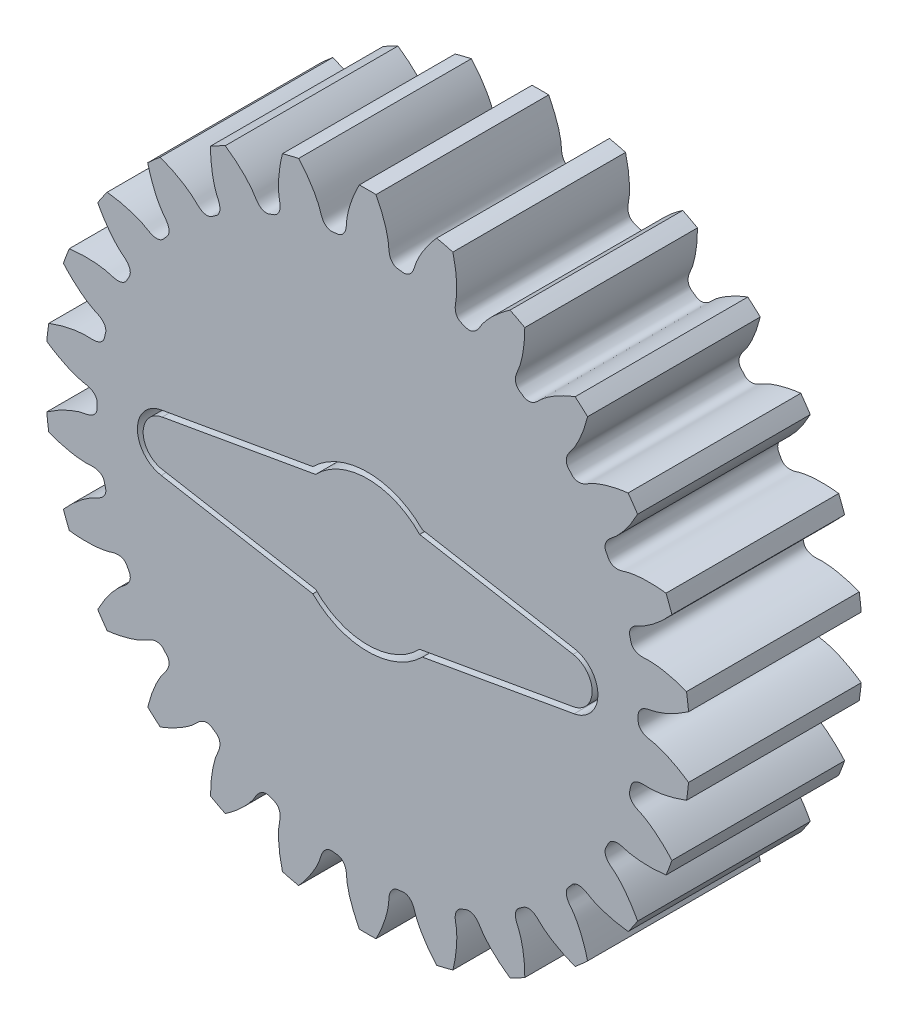
SolidWorks part; units mm, degrees
ref_plane "Front Plane" through (0, 0, 0) normal (0, 0, 1) x (1, 0, 0)
ref_plane "Top Plane" through (0, 0, 0) normal (0, 1, 0) x (1, 0, 0)
ref_plane "Right Plane" through (0, 0, 0) normal (1, 0, 0) x (0, 0, -1)
ref_axis "Axis1" through (0, 0, 55) along (0, 0, -1)
sketch "旋转草图小直齿轮" plane through (0, 0, 0) normal (1, 0, 0) x (0, 0, -1)
  line L0 (0, 0) -> (1, 0) construction
  line L1 (-7.5, 0) -> (-7.5, 28)
  line L2 (-7.5, 28) -> (7.5, 28)
  line L3 (7.5, 28) -> (7.5, 0)
  line L4 (7.5, 0) -> (-7.5, 0)
  dimension "Side1" = 7.5
  dimension "OutsideRadius" = 28
  dimension "Side2" = 7.5
revolve "小直齿轮" add sketch "旋转草图小直齿轮" angle 360 about L0
sketch "齿草图小直齿轮" plane through (0, 0, 0) normal (0, 0, 1) x (1, 0, 0)
  arc A0 (27.9679, 2.7212) -> (27.9679, -2.7212) centre (0, 0) cw
  spline S0 degree 3 poles (27.9679, -2.7212) (27.7638, -2.5774) (27.4599, -2.3753) (27.0547, -2.1308) (26.7715, -1.9706) (26.5013, -1.8278) (26.2448, -1.7014) (26.0028, -1.5905) (25.7759, -1.4943) (25.5647, -1.4117) (25.3698, -1.3417) (25.1918, -1.2835) (25.0311, -1.2359) (24.8881, -1.198) (24.7634, -1.1686) (24.6015, -1.1352) (24.461, -1.1147) (24.34, -1.0852) (24.2853, -1.0704) (24.2318, -1.0542) (24.1794, -1.0366) (24.1279, -1.0175) (24.0774, -0.9966) (24.0276, -0.9738) (23.9785, -0.9488) (23.9299, -0.9214) (23.8818, -0.891) (23.8341, -0.8573) (23.7869, -0.8195) (23.7403, -0.777) (23.6946, -0.7291) (23.6504, -0.6747) (23.6089, -0.6131) (23.5712, -0.5439) (23.5394, -0.4668) (23.5153, -0.3828) (23.502, -0.2987) (23.4964, -0.1705) (23.5027, 0) (23.4964, 0.1705) (23.502, 0.2987) (23.5153, 0.3828) (23.5394, 0.4668) (23.5712, 0.5439) (23.6089, 0.6131) (23.6504, 0.6747) (23.6946, 0.7291) (23.7403, 0.777) (23.7869, 0.8195) (23.8341, 0.8573) (23.8818, 0.891) (23.9299, 0.9214) (23.9785, 0.9488) (24.0276, 0.9738) (24.0774, 0.9966) (24.1279, 1.0175) (24.1794, 1.0366) (24.2318, 1.0542) (24.2853, 1.0704) (24.34, 1.0852) (24.461, 1.1147) (24.6015, 1.1352) (24.7634, 1.1686) (24.8881, 1.198) (25.0311, 1.2359) (25.1918, 1.2835) (25.3698, 1.3417) (25.5647, 1.4117) (25.7759, 1.4943) (26.0028, 1.5905) (26.2448, 1.7014) (26.5013, 1.8278) (26.7715, 1.9706) (27.0547, 2.1308) (27.4599, 2.3753) (27.7638, 2.5774) (27.9679, 2.7212) knots 0 0 0 0 0.067642 0.098793 0.128164 0.155755 0.181566 0.205597 0.227848 0.248319 0.267009 0.28392 0.29905 0.312401 0.323971 0.333762 0.357174 0.362366 0.367478 0.37252 0.377507 0.382456 0.387386 0.39232 0.397282 0.402306 0.407425 0.41268 0.418119 0.423791 0.429751 0.436051 0.442738 0.449842 0.457364 0.465268 0.473469 0.480354 0.5 0.519646 0.526531 0.534732 0.542636 0.550158 0.557262 0.563949 0.570249 0.576209 0.581881 0.58732 0.592575 0.597694 0.602718 0.60768 0.612614 0.617544 0.622493 0.62748 0.632522 0.637634 0.642826 0.666238 0.676029 0.687599 0.70095 0.71608 0.732991 0.751681 0.772152 0.794403 0.818434 0.844245 0.871836 0.901207 0.932358 1 1 1 1
extrude "齿拉伸切除小直齿轮" cut sketch "齿草图小直齿轮" against normal blind 7.5 and the other way blind 7.5
pattern_circular "齿形小直齿轮" count 26 every 13.846 about axis through (0, 0, 55) along (0, 0, -1) of "齿拉伸切除小直齿轮"
sketch "辅助草图小直齿轮" plane through (0, 0, 0) normal (0, 0, 1) x (1, 0, 0)
  circle A0 centre (0, 0) radius 26 construction
  circle A1 centre (0, 0) radius 24.432 construction
  circle A2 centre (0, 0) radius 24.5849 construction
  circle A3 centre (0, 0) radius 28 construction
  circle A4 centre (0, 0) radius 23.5 construction
  dimension "PitchDiameter" = 52
  dimension "BaseDiameter" = 48.864
  dimension "FormDiameter" = 49.1697
  dimension "MajorDiameter" = 56
  dimension "MinorDiameter" = 47
sketch "Sketch5" plane through (0, 0, 7.5) normal (0, 0, 1) x (1, 0, 0)
  circle A0 centre (0, 0) radius 1.5
  dimension "D1" = 3
extrude "Extrude2" cut sketch "Sketch5" against normal through all
sketch "Sketch6" plane through (0, 0, 7.5) normal (0, 0, 1) x (1, 0, 0)
  line L0 (20, 0) -> (-20, 0) construction
  line L1 (17.9341, -2.462) -> (4.7611, -4.7848)
  line L2 (17.9341, 2.462) -> (4.7611, 4.7848)
  line L3 (0, 0) -> (0, -13.8039) construction
  line L4 (-17.9341, 2.462) -> (-4.7611, 4.7848)
  line L5 (-17.9341, -2.462) -> (-4.7611, -4.7848)
  arc A0 (4.7611, 4.7848) -> (-4.7611, 4.7848) centre (0, 0) ccw
  arc A1 (-17.9341, -2.462) -> (-17.9341, 2.462) centre (-17.5, 0) cw
  arc A2 (17.9341, -2.462) -> (17.9341, 2.462) centre (17.5, 0) ccw
  arc A4 (-4.7611, -4.7848) -> (4.7611, -4.7848) centre (0, 0) ccw
  point P6 (0, 0)
  dimension "D1" = 13.5
  dimension "D4" = 5
  dimension "D2" = 40
  dimension "D6" = 20
extrude "Extrude3" cut sketch "Sketch6" against normal blind 2.5
sketch "Sketch7" plane through (0, 0, -7.5) normal (0, 0, -1) x (-1, 0, 0)
  line L0 (0, 0) -> (-8.197, 22.0229)
  spline S0 degree 3 poles (-12.3671, 25.1208) (-12.1929, 25.0009) (-11.9283, 24.8095) (-11.586, 24.541) (-11.3359, 24.333) (-11.1065, 24.131) (-10.8974, 23.936) (-10.7079, 23.7491) (-10.5374, 23.571) (-10.3853, 23.4028) (-10.2508, 23.2454) (-10.1332, 23.0996) (-10.0318, 22.9662) (-9.9456, 22.846) (-9.8739, 22.7398) (-9.7852, 22.6003) (-9.7162, 22.4762) (-9.6457, 22.3735) (-9.6125, 22.3276) (-9.5784, 22.2833) (-9.5434, 22.2405) (-9.5072, 22.1992) (-9.4698, 22.1593) (-9.4308, 22.1209) (-9.39, 22.0838) (-9.3472, 22.0481) (-9.3017, 22.0139) (-9.2533, 21.9813) (-9.2012, 21.9505) (-9.145, 21.922) (-9.0839, 21.8963) (-9.0174, 21.8743) (-8.9451, 21.8572) (-8.867, 21.8466) (-8.7837, 21.8441) (-8.6966, 21.8515) (-8.6132, 21.8689) (-8.4913, 21.909) (-8.3342, 21.9754) (-8.1725, 22.0299) (-8.0546, 22.0807) (-7.9807, 22.123) (-7.9107, 22.1752) (-7.8499, 22.2323) (-7.7985, 22.2921) (-7.7557, 22.3528) (-7.7205, 22.4133) (-7.6919, 22.4731) (-7.6687, 22.5317) (-7.6501, 22.5893) (-7.6355, 22.6458) (-7.6242, 22.7016) (-7.6157, 22.7567) (-7.6098, 22.8115) (-7.6061, 22.8661) (-7.6045, 22.9208) (-7.6049, 22.9757) (-7.607, 23.031) (-7.6109, 23.0867) (-7.6164, 23.1431) (-7.6318, 23.2667) (-7.6624, 23.4053) (-7.6885, 23.5686) (-7.7053, 23.6956) (-7.7205, 23.8427) (-7.733, 24.0099) (-7.7417, 24.197) (-7.7454, 24.404) (-7.7431, 24.6308) (-7.7336, 24.8771) (-7.7157, 25.1427) (-7.6885, 25.4273) (-7.6508, 25.7306) (-7.6014, 26.0522) (-7.5233, 26.4801) (-7.4521, 26.7988) (-7.4013, 27.0041) knots 0.010365 0.010365 0.010365 0.010365 0.067642 0.098793 0.128164 0.155755 0.181566 0.205597 0.227848 0.248319 0.267009 0.28392 0.29905 0.312401 0.323971 0.333762 0.357174 0.362366 0.367478 0.37252 0.377507 0.382456 0.387386 0.39232 0.397282 0.402306 0.407425 0.41268 0.418119 0.423791 0.429751 0.436051 0.442738 0.449842 0.457364 0.465268 0.473469 0.480354 0.5 0.519646 0.526531 0.534732 0.542636 0.550158 0.557262 0.563949 0.570249 0.576209 0.581881 0.58732 0.592575 0.597694 0.602718 0.60768 0.612614 0.617544 0.622493 0.62748 0.632522 0.637634 0.642826 0.666238 0.676029 0.687599 0.70095 0.71608 0.732991 0.751681 0.772152 0.794403 0.818434 0.844245 0.871836 0.901207 0.932358 0.989635 0.989635 0.989635 0.989635 construction
sketch "Sketch8" plane through (0, 0, 5) normal (0, 0, 1) x (1, 0, 0)
  line L8 (-17.8473, -1.9696) -> (-4.5165, -4.3202)
  line L9 (4.5165, -4.3202) -> (17.8473, -1.9696)
  line L10 (17.8473, 1.9696) -> (4.5165, 4.3202)
  line L11 (-4.5165, 4.3202) -> (-17.8473, 1.9696)
  line L12 (-17.8473, -1.9696) -> (-4.5165, -4.3202)
  line L13 (4.5165, -4.3202) -> (17.8473, -1.9696)
  line L14 (17.8473, 1.9696) -> (4.5165, 4.3202)
  line L15 (-4.5165, 4.3202) -> (-17.8473, 1.9696)
  arc A8 (-17.8473, 1.9696) -> (-17.8473, -1.9696) centre (-17.5, 0) ccw
  arc A9 (-4.5165, -4.3202) -> (4.5165, -4.3202) centre (0, 0) ccw
  arc A10 (17.8473, -1.9696) -> (17.8473, 1.9696) centre (17.5, 0) ccw
  arc A11 (4.5165, 4.3202) -> (-4.5165, 4.3202) centre (0, 0) ccw
  arc A12 (-17.8473, 1.9696) -> (-17.8473, -1.9696) centre (-17.5, 0) ccw
  arc A13 (-4.5165, -4.3202) -> (4.5165, -4.3202) centre (0, 0) ccw
  arc A14 (17.8473, -1.9696) -> (17.8473, 1.9696) centre (17.5, 0) ccw
  arc A15 (4.5165, 4.3202) -> (-4.5165, 4.3202) centre (0, 0) ccw
  dimension "D1" = 0.5
extrude "Extrude4" add sketch "Sketch8" along normal up to surface (2.5 mm away) up to face at (0, 0, 7.5)
